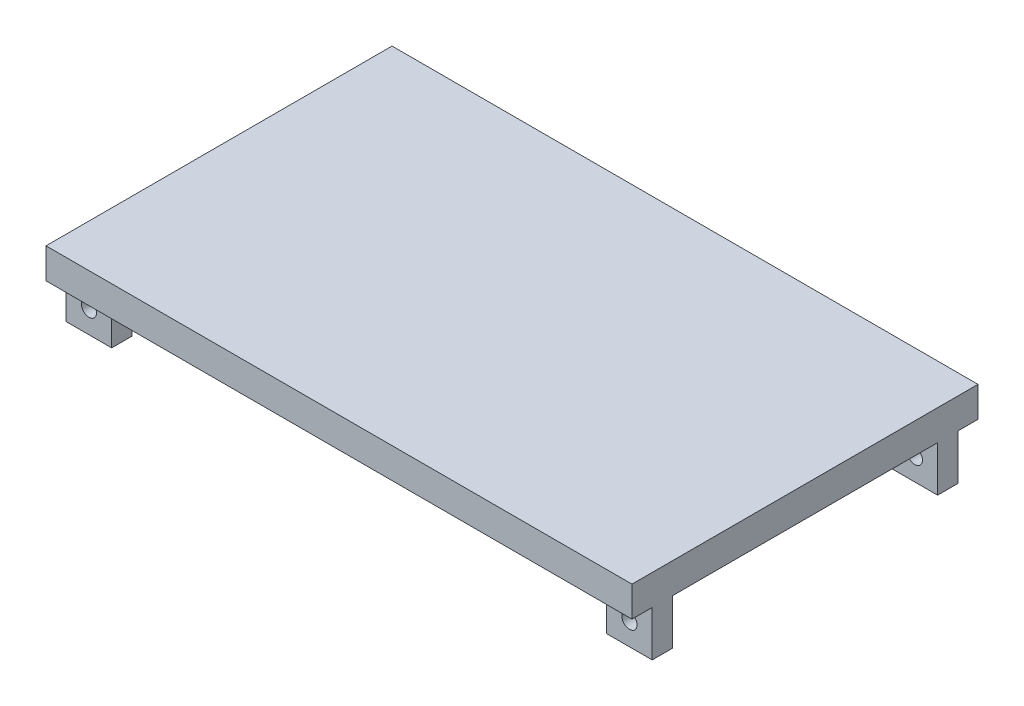
SolidWorks part; units mm, degrees
ref_plane "Front Plane" through (0, 0, 0) normal (0, 0, 1) x (1, 0, 0)
ref_plane "Top Plane" through (0, 0, 0) normal (0, 1, 0) x (1, 0, 0)
ref_plane "Right Plane" through (0, 0, 0) normal (1, 0, 0) x (0, 0, -1)
sketch "Sketch1" plane through (0, 0, 0) normal (0, 1, 0) x (1, 0, 0)
  line L1 (0, 0) -> (-116, 0)
  line L2 (0, 0) -> (0, 34.25)
  line L3 (0, 34.25) -> (-116, 34.25)
  line L4 (-116, 0) -> (-116, 34.25)
  dimension "D1" = 116
  dimension "D2" = 34.25
extrude "Boss-Extrude2" add sketch "Sketch1" along normal blind 6
sketch "Sketch3" plane through (0, 0, 0) normal (0, -1, 0) x (1, 0, 0)
  line L0 (-116, -34.25) -> (-116, 0) construction
  line L1 (-116, -4) -> (-107, -4)
  line L2 (-116, -4) -> (-116, -8)
  line L3 (-116, -8) -> (-107, -8)
  line L4 (-107, -4) -> (-107, -8)
  line L5 (0, 0) -> (0, -34.25) construction
  line L6 (0, -4) -> (-9, -4)
  line L7 (0, -4) -> (0, -8)
  line L8 (0, -8) -> (-9, -8)
  line L9 (-9, -4) -> (-9, -8)
  line L10 (-116, 0) -> (0, 0) construction
  dimension "D1" = 4
  dimension "D2" = 4
  dimension "D3" = 9
  dimension "D4" = 9
  dimension "D5" = 4
  dimension "D6" = 4
extrude "Boss-Extrude3" add sketch "Sketch3" along normal blind 9
sketch "Sketch4" plane through (0, 0, -4) normal (0, 0, 1) x (1, 0, 0)
  line L0 (-116, -9) -> (-116, 0) construction
  line L1 (-107, -9) -> (-116, -9) construction
  line L2 (0, -9) -> (-9, -9) construction
  line L3 (0, -9) -> (0, 0) construction
  circle A0 centre (-111.5, -4.5) radius 1.5
  circle A1 centre (-4.5, -4.5) radius 1.5
  dimension "D1" = 3
  dimension "D2" = 4.5
  dimension "D3" = 4.5
  dimension "D4" = 4.5
  dimension "D5" = 3
  dimension "D6" = 4.5
extrude "Cut-Extrude1" cut sketch "Sketch4" against normal through all
mirror "Mirror1" about plane through (0, 6, -34.25) normal (0, 0, 1) of "Cut-Extrude1", "Boss-Extrude3", "Boss-Extrude2"
